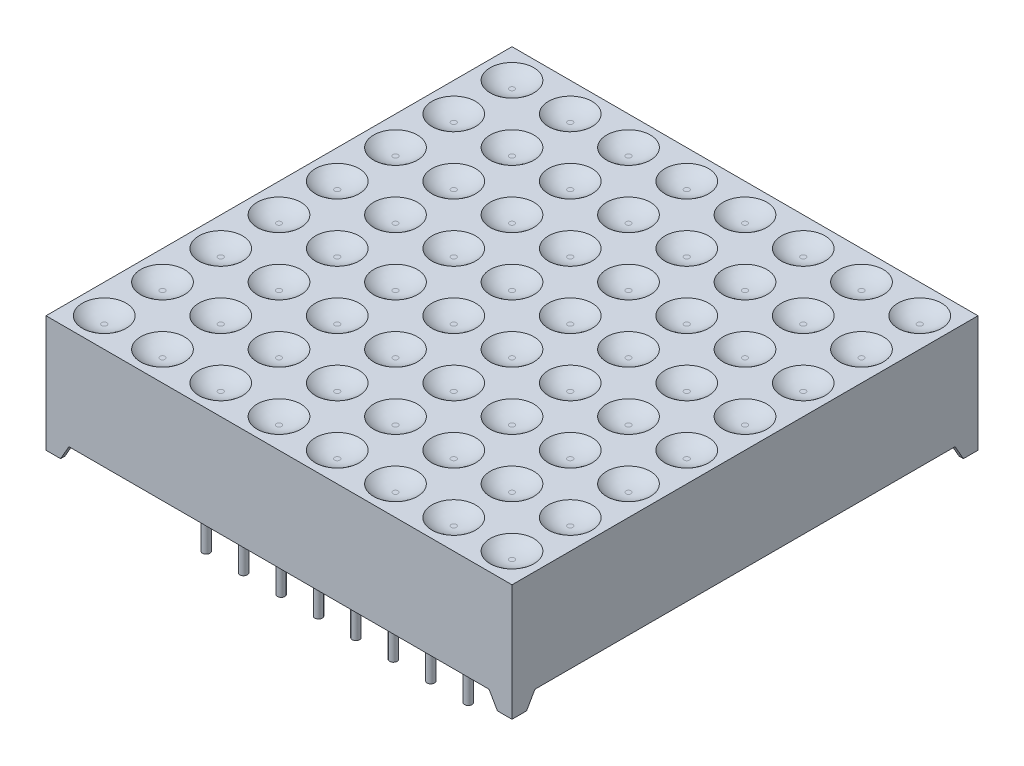
SolidWorks part; units mm, degrees
ref_plane "Front" through (0, 0, 0) normal (0, 0, 1) x (1, 0, 0)
ref_plane "Top" through (0, 0, 0) normal (0, 1, 0) x (1, 0, 0)
ref_plane "Right" through (0, 0, 0) normal (1, 0, 0) x (0, 0, -1)
sketch "Sketch1" plane through (0, 0, 0) normal (0, 1, 0) x (1, 0, 0)
  line L1 (-16, -16) -> (16, -16)
  line L2 (-16, -16) -> (-16, 16)
  line L3 (-16, 16) -> (16, 16)
  line L4 (16, -16) -> (16, 16)
  line L5 (-16, -16) -> (16, 16) construction
  line L6 (-16, 16) -> (16, -16) construction
  point P0 (0, 0)
  dimension "D1" = 32
extrude "Boss-Extrude1" add sketch "Sketch1" along normal mid plane 8
sketch "Sketch2" plane through (0, -4, 0) normal (0, -1, 0) x (1, 0, 0)
  line L0 (-16, -16) -> (-16, 16) construction
  line L1 (15.7, 15.7) -> (-15.7, 15.7)
  line L2 (15.7, 15.7) -> (15.7, -15.7)
  line L3 (15.7, -15.7) -> (-15.7, -15.7)
  line L4 (-15.7, 15.7) -> (-15.7, -15.7)
  line L5 (15.7, 15.7) -> (-15.7, -15.7) construction
  line L6 (15.7, -15.7) -> (-15.7, 15.7) construction
  line L7 (16, -16) -> (-16, -16) construction
  point P0 (0, 0)
  dimension "D1" = 0.3
  dimension "D2" = 0.3
extrude "Cut-Extrude1" cut sketch "Sketch2" against normal blind 1.5
sketch "Sketch3" plane through (0, 0, 16) normal (0, 0, 1) x (1, 0, 0)
  line L0 (-15, -4) -> (-14.4226, -3)
  line L1 (-16, -4) -> (16, -4) construction
  line L2 (-14.4226, -3) -> (14.4226, -3)
  line L3 (0, -3) -> (0, 0) construction
  line L4 (-16, 4) -> (-16, -4) construction
  line L5 (15, -4) -> (14.4226, -3)
  line L6 (-15, -4) -> (15, -4)
  dimension "D1" = 1
  dimension "D2" = 60
  dimension "D3" = 1
extrude "Cut-Extrude2" cut sketch "Sketch3" against normal through all
sketch "Sketch4" plane through (-16, 0, 0) normal (-1, 0, 0) x (0, 0, 1)
  line L0 (-15, -4) -> (-14.4226, -3)
  line L1 (-16, -4) -> (16, -4) construction
  line L2 (-14.4226, -3) -> (14.4226, -3)
  line L3 (0, -3) -> (0, 0) construction
  line L4 (-16, 4) -> (-16, -4) construction
  line L5 (15, -4) -> (14.4226, -3)
  line L6 (-15, -4) -> (15, -4)
  dimension "D1" = 60
  dimension "D2" = 1
  dimension "D3" = 1
extrude "Cut-Extrude3" cut sketch "Sketch4" against normal through all
sketch "Sketch5" plane through (0, 4, 0) normal (0, 1, 0) x (1, 0, 0)
  line L0 (16, -16) -> (16, 16) construction
  circle A0 centre (-14, 14) radius 1.5
  circle A1 centre (-10, 14) radius 1.5
  circle A2 centre (-6, 14) radius 1.5
  circle A3 centre (-2, 14) radius 1.5
  circle A4 centre (2, 14) radius 1.5
  circle A5 centre (6, 14) radius 1.5
  circle A6 centre (10, 14) radius 1.5
  circle A7 centre (14, 14) radius 1.5
  circle A8 centre (-14, 10) radius 1.5
  circle A9 centre (-10, 10) radius 1.5
  circle A10 centre (-6, 10) radius 1.5
  circle A11 centre (-2, 10) radius 1.5
  circle A12 centre (2, 10) radius 1.5
  circle A13 centre (6, 10) radius 1.5
  circle A14 centre (10, 10) radius 1.5
  circle A15 centre (14, 10) radius 1.5
  circle A16 centre (-14, 6) radius 1.5
  circle A17 centre (-10, 6) radius 1.5
  circle A18 centre (-6, 6) radius 1.5
  circle A19 centre (-2, 6) radius 1.5
  circle A20 centre (2, 6) radius 1.5
  circle A21 centre (6, 6) radius 1.5
  circle A22 centre (10, 6) radius 1.5
  circle A23 centre (14, 6) radius 1.5
  circle A24 centre (-14, 2) radius 1.5
  circle A25 centre (-10, 2) radius 1.5
  circle A26 centre (-6, 2) radius 1.5
  circle A27 centre (-2, 2) radius 1.5
  circle A28 centre (2, 2) radius 1.5
  circle A29 centre (6, 2) radius 1.5
  circle A30 centre (10, 2) radius 1.5
  circle A31 centre (14, 2) radius 1.5
  circle A32 centre (-14, -2) radius 1.5
  circle A33 centre (-10, -2) radius 1.5
  circle A34 centre (-6, -2) radius 1.5
  circle A35 centre (-2, -2) radius 1.5
  circle A36 centre (2, -2) radius 1.5
  circle A37 centre (6, -2) radius 1.5
  circle A38 centre (10, -2) radius 1.5
  circle A39 centre (14, -2) radius 1.5
  circle A40 centre (-14, -6) radius 1.5
  circle A41 centre (-10, -6) radius 1.5
  circle A42 centre (-6, -6) radius 1.5
  circle A43 centre (-2, -6) radius 1.5
  circle A44 centre (2, -6) radius 1.5
  circle A45 centre (6, -6) radius 1.5
  circle A46 centre (10, -6) radius 1.5
  circle A47 centre (14, -6) radius 1.5
  circle A48 centre (-14, -10) radius 1.5
  circle A49 centre (-10, -10) radius 1.5
  circle A50 centre (-6, -10) radius 1.5
  circle A51 centre (-2, -10) radius 1.5
  circle A52 centre (2, -10) radius 1.5
  circle A53 centre (6, -10) radius 1.5
  circle A54 centre (10, -10) radius 1.5
  circle A55 centre (14, -10) radius 1.5
  circle A56 centre (-14, -14) radius 1.5
  circle A57 centre (-10, -14) radius 1.5
  circle A58 centre (-6, -14) radius 1.5
  circle A59 centre (-2, -14) radius 1.5
  circle A60 centre (2, -14) radius 1.5
  circle A61 centre (6, -14) radius 1.5
  circle A62 centre (10, -14) radius 1.5
  circle A63 centre (14, -14) radius 1.5
  dimension "D1" = 3
  dimension "D2" = 14
  dimension "D3" = 14
  dimension "D6" = 2
  dimension "D7" = 6
  dimension "D4" = 8
  dimension "D5" = 8
extrude "Cut-Extrude4" cut sketch "Sketch5" against normal blind 0.5
fillet "Fillet1" radius 2 64 edges at (-10, 3.5, 15.5) (-14, 3.5, 15.5) (-6, 3.5, 15.5) (-2, 3.5, 15.5) (2, 3.5, 15.5) (6, 3.5, 15.5) (10, 3.5, 15.5) (14, 3.5, 15.5) (-14, 3.5, 11.5) (-10, 3.5, 11.5) (-6, 3.5, 11.5) (-2, 3.5, 11.5) (10, 3.5, 11.5) (6, 3.5, 11.5) (2, 3.5, 11.5) (2, 3.5, 7.5) (-2, 3.5, 7.5) (-6, 3.5, 7.5) (-10, 3.5, 7.5) (-14, 3.5, 7.5) (-6, 3.5, 3.5) (-10, 3.5, 3.5) (-14, 3.5, 3.5) (-14, 3.5, -0.5) (14, 3.5, 11.5) (6, 3.5, 7.5) (10, 3.5, 7.5) (14, 3.5, 7.5) (-2, 3.5, 3.5) (2, 3.5, 3.5) (6, 3.5, 3.5) (10, 3.5, 3.5) (14, 3.5, 3.5) (-10, 3.5, -0.5) (-6, 3.5, -0.5) (-2, 3.5, -0.5) (2, 3.5, -0.5) (6, 3.5, -0.5) (10, 3.5, -0.5) (14, 3.5, -0.5) (2, 3.5, -4.5) (-2, 3.5, -4.5) (-6, 3.5, -4.5) (-10, 3.5, -4.5) (-14, 3.5, -4.5) (-6, 3.5, -8.5) (-10, 3.5, -8.5) (-14, 3.5, -8.5) (-14, 3.5, -12.5) (-10, 3.5, -12.5) (-6, 3.5, -12.5) (-2, 3.5, -12.5) (-2, 3.5, -8.5) (6, 3.5, -4.5) (14, 3.5, -4.5) (10, 3.5, -4.5) (2, 3.5, -12.5) (2, 3.5, -8.5) (6, 3.5, -8.5) (14, 3.5, -8.5) (10, 3.5, -8.5) (6, 3.5, -12.5) (14, 3.5, -12.5) (10, 3.5, -12.5)
sketch "Sketch6" plane through (0, -2.5, 0) normal (0, -1, 0) x (1, 0, 0)
  circle A0 centre (-9, 12) radius 0.255
  circle A1 centre (-6.4286, 12) radius 0.255
  circle A2 centre (-3.8571, 12) radius 0.255
  circle A3 centre (-1.2857, 12) radius 0.255
  circle A4 centre (1.2857, 12) radius 0.255
  circle A5 centre (3.8571, 12) radius 0.255
  circle A6 centre (6.4286, 12) radius 0.255
  circle A7 centre (9, 12) radius 0.255
  circle A8 centre (-9, -12) radius 0.255
  circle A9 centre (-6.4286, -12) radius 0.255
  circle A10 centre (-3.8571, -12) radius 0.255
  circle A11 centre (-1.2857, -12) radius 0.255
  circle A12 centre (1.2857, -12) radius 0.255
  circle A13 centre (3.8571, -12) radius 0.255
  circle A14 centre (6.4286, -12) radius 0.255
  circle A15 centre (9, -12) radius 0.255
  dimension "D1" = 0.51
  dimension "D2" = 9
  dimension "D3" = 12
  dimension "D7" = 9
  dimension "D8" = 2.5714
  dimension "D6" = 9
  dimension "D9" = 12
  dimension "D4" = 8
  dimension "D5" = 2
extrude "Boss-Extrude2" add sketch "Sketch6" along normal blind 6
